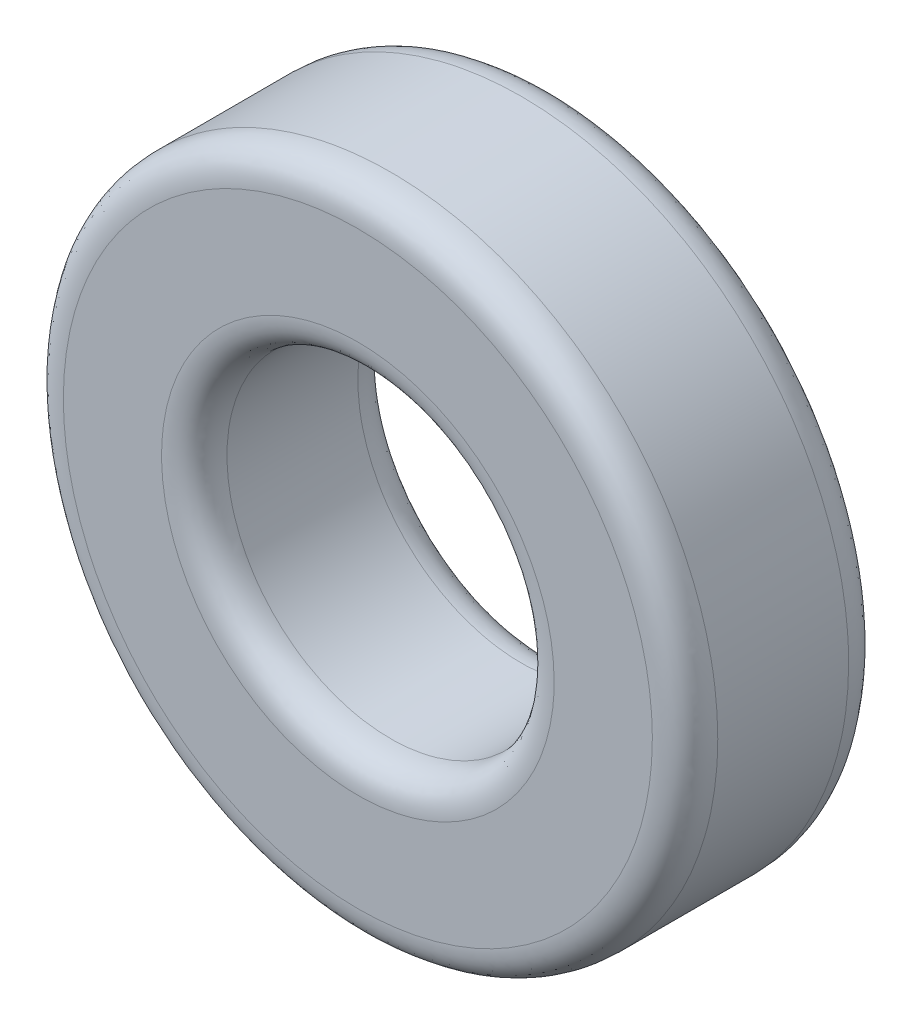
SolidWorks part; units mm, degrees
ref_plane "Front Plane" through (0, 0, 0) normal (0, 0, 1) x (1, 0, 0)
ref_plane "Top Plane" through (0, 0, 0) normal (0, 1, 0) x (1, 0, 0)
ref_plane "Right Plane" through (0, 0, 0) normal (1, 0, 0) x (0, 0, -1)
sketch "Sketch1" plane through (0, 0, 0) normal (0, 0, 1) x (1, 0, 0)
  circle A0 centre (0, 0) radius 2.5
  circle A1 centre (0, 0) radius 5
  dimension "D1" = 5
  dimension "D2" = 10
extrude "Boss-Extrude1" add sketch "Sketch1" along normal blind 3
fillet "Fillet1" radius 0.5 4 edges at (5, 0, 3) (2.5, 0, 0) (2.5, 0, 3) (5, 0, 0) conic rho 0.5
